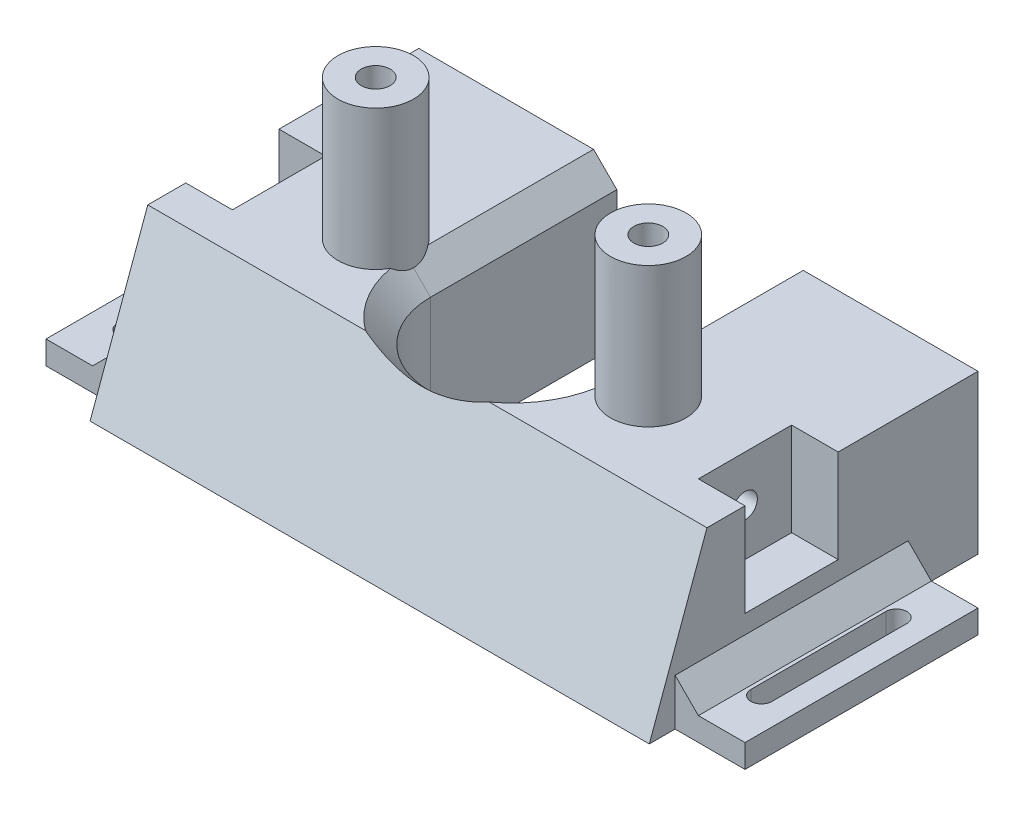
SolidWorks part; units mm, degrees
ref_plane "Front Plane" through (0, 0, 0) normal (0, 0, 1) x (1, 0, 0)
ref_plane "Top Plane" through (0, 0, 0) normal (0, 1, 0) x (1, 0, 0)
ref_plane "Right Plane" through (0, 0, 0) normal (1, 0, 0) x (0, 0, -1)
sketch "Sketch1" plane through (0, 0, 0) normal (0, 1, 0) x (1, 0, 0)
  line L1 (-60, -40) -> (60, -40)
  line L2 (-60, -40) -> (-60, 40)
  line L3 (-60, 40) -> (60, 40)
  line L4 (60, -40) -> (60, 40)
  line L5 (-60, -40) -> (60, 40) construction
  line L6 (-60, 40) -> (60, -40) construction
  point P0 (0, 0)
  dimension "D1" = 120
  dimension "D2" = 80
extrude "Boss-Extrude1" add sketch "Sketch1" along normal blind 60
sketch "Sketch2" plane through (0, 60, 0) normal (0, 1, 0) x (1, 0, 0)
  line L0 (-17.5, 0) -> (-17.5, 40)
  line L1 (-17.5, 40) -> (17.5, 40)
  line L2 (60, 40) -> (-60, 40) construction
  line L3 (17.5, 40) -> (17.5, 0)
  arc A0 (-17.5, 0) -> (17.5, 0) centre (0, 0) ccw
  dimension "D1" = 35
extrude "Cut-Extrude1" cut sketch "Sketch2" against normal through all
sketch "Sketch10" plane through (0, 60, 0) normal (0, 1, 0) x (1, 0, 0)
  circle A0 centre (-29.25, 0) radius 3 construction
  circle A1 centre (29.25, 0) radius 3 construction
  circle A2 centre (-29.25, 0) radius 3 construction
  circle A3 centre (29.25, 0) radius 3 construction
  circle A4 centre (-29.25, 0) radius 3.1
  circle A5 centre (29.25, 0) radius 3.1
  dimension "D1" = 0.1
extrude "Cut-Extrude4" cut sketch "Sketch10" against normal blind 20
sketch "Sketch4" plane through (0, 60, 0) normal (0, 1, 0) x (1, 0, 0)
  line L0 (0, 0) -> (0, 69.3912) construction
  circle A8 centre (29.25, 0) radius 3.1 construction
  circle A9 centre (-29.25, 0) radius 3.1 construction
  circle A10 centre (29.25, 0) radius 3.1
  circle A11 centre (-29.25, 0) radius 3.1
  circle A12 centre (29.25, 0) radius 8.1
  circle A13 centre (-29.25, 0) radius 8.1
  dimension "D1" = 5
extrude "Boss-Extrude2" add sketch "Sketch4" along normal blind 30
ref_plane "Plane2" through (32.35, 0, 0) normal (-1, 0, 0) x (0, 0, 1)
sketch "Sketch5" plane through (60, 0, 0) normal (1, 0, 0) x (0, 0, -1)
  line L0 (-40, 60) -> (40, 60) construction
  line L1 (-10, 60) -> (10, 60)
  line L2 (-10, 60) -> (-10, 40)
  line L3 (-10, 40) -> (10, 40)
  line L4 (10, 60) -> (10, 40)
  line L5 (-40, 0) -> (40, 0) construction
  point P6 (0, 40)
  dimension "D1" = 20
  dimension "D2" = 40
extrude "Cut-Extrude3" cut sketch "Sketch5" against normal blind 10
sketch "Sketch6" plane through (50, 0, 0) normal (1, 0, 0) x (0, 0, -1)
  line L1 (-10, 40) -> (10, 40) construction
  circle A0 centre (0, 50) radius 2.65
  dimension "D1" = 5.3
  dimension "D2" = 10
extrude "Cut-Extrude5" cut sketch "Sketch6" against normal up to next
mirror "Mirror2" about plane through (0, 0, 0) normal (1, 0, 0) of "Cut-Extrude5", "Cut-Extrude3"
draft "Draft2" type of draft neutral plane draft angle 20 faces to draft 1 face at (0, 30, 40) neutral plane through (0, 0, 0) neutral plane normal (0, -1, 0) reverse direction yes parameters "D1"=20
chamfer "Chamfer3" distance 5 angle 45 3 edges at (17.5, 60, -20) (0, 60, 17.5) (-17.5, 60, -20)
sketch "Sketch11" plane through (60, 0, 0) normal (1, 0, 0) x (0, 0, -1)
  line L0 (-40, 0) -> (40, 0) construction
  line L1 (-46.3087, 26) -> (49.4653, 26)
  line L2 (-46.3087, 26) -> (-46.3087, 0)
  line L3 (-46.3087, 0) -> (49.4653, 0)
  line L4 (49.4653, 26) -> (49.4653, 0)
  dimension "D1" = 26
extrude "Cut-Extrude6" cut sketch "Sketch11" against normal through all
sketch "Sketch13" plane through (0, 26, 0) normal (0, -1, 0) x (1, 0, 0)
  line L1 (60, 25) -> (75, 25)
  line L2 (60, 25) -> (60, -25)
  line L3 (60, -25) -> (75, -25)
  line L4 (75, 25) -> (75, -25)
  line L5 (68, 14.4786) -> (68, -14.4786) construction
  line L6 (70.25, 14.4786) -> (70.25, -14.4786)
  line L7 (65.75, 14.4786) -> (65.75, -14.4786)
  line L8 (60, -10) -> (60, -40) construction
  line L9 (60, -40) -> (22.5, -40) construction
  arc A0 (70.25, 14.4786) -> (65.75, 14.4786) centre (68, 14.4786) ccw
  arc A1 (65.75, -14.4786) -> (70.25, -14.4786) centre (68, -14.4786) ccw
  point P8 (68, 0)
  point P13 (69.2051, 0)
  point P14 (0, 0)
  point P17 (75, 0)
  dimension "D1" = 28.9573
  dimension "D2" = 4.5
  dimension "D3" = 50
  dimension "D4" = 15
  dimension "D5" = 15
  dimension "D6" = 8
extrude "Boss-Extrude3" add sketch "Sketch13" against normal blind 5
mirror "Mirror3" about plane through (0, 0, 0) normal (1, 0, 0) of "Boss-Extrude3"
chamfer "Chamfer4" distance 5 angle 45 2 edges at (-60, 31, 0) (60, 31, 0)
